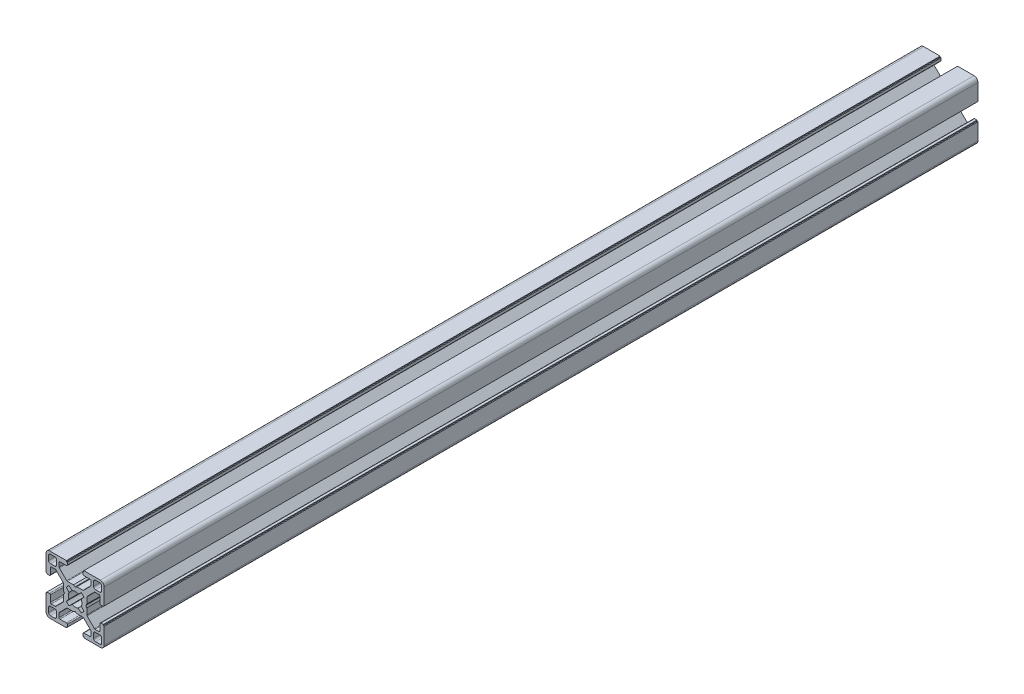
SolidWorks part; units mm, degrees
ref_plane "Front Plane" through (0, 0, 0) normal (0, 0, 1) x (1, 0, 0)
ref_plane "Top Plane" through (0, 0, 0) normal (0, 1, 0) x (1, 0, 0)
ref_plane "Right Plane" through (0, 0, 0) normal (1, 0, 0) x (0, 0, -1)
sketch "Sketch1" plane through (0, 0, 0) normal (0, 0, 1) x (1, 0, 0)
  line L0 (-15, 0) -> (15, 0) construction
  line L1 (0, -15) -> (0, 15) construction
  line L2 (-4.5, 15) -> (4.5, 15) construction
  line L3 (-4, -15) -> (4, -15) construction
  line L4 (-4.5, 15) -> (-4.5, 14.5)
  line L5 (-4.5, 14.5) -> (-4, 14.5)
  line L6 (-4, 14.5) -> (-4, 13.29)
  line L7 (-4.5, 12.79) -> (-7.7675, 12.79)
  line L8 (-8.2675, 12.29) -> (-8.2675, 10.2707)
  line L9 (-8.1211, 9.9171) -> (-4.3504, 6.1464)
  line L10 (-3.9968, 6) -> (0, 6)
  line L11 (0, 0) -> (-15, 15) construction
  line L12 (-4.5, 15) -> (-12.968, 15)
  line L14 (-12.705, 9.5135) -> (-10.5135, 9.5135)
  line L15 (-13.705, 10.5135) -> (-13.705, 12.705)
  line L16 (-12.705, 13.705) -> (-10.5135, 13.705)
  line L17 (-9.5135, 10.5135) -> (-9.5135, 12.705)
  line L18 (-13.705, 9.5135) -> (-9.5135, 13.705) construction
  line L19 (-13.705, 13.705) -> (-9.5135, 9.5135) construction
  line L20 (-3.1568, 4.5038) -> (-1.5303, 3.1477) construction
  line L21 (-4.5038, 3.1568) -> (-3.1477, 1.5303) construction
  line L22 (-6, 3.9968) -> (-6, 0)
  line L23 (-9.9171, 8.1211) -> (-6.1464, 4.3504)
  line L24 (-15, 4.5) -> (-15, 12.968)
  line L25 (-12.29, 8.2675) -> (-10.2707, 8.2675)
  line L26 (-12.79, 4.5) -> (-12.79, 7.7675)
  line L27 (-14.5, 4) -> (-13.29, 4)
  line L28 (-14.5, 4.5) -> (-14.5, 4)
  line L29 (-15, 4.5) -> (-14.5, 4.5)
  circle A0 centre (0, 0) radius 3.5
  arc A1 (-12.968, 15) -> (-15, 12.968) centre (-12.968, 12.968) ccw
  circle A2 centre (0, 0) radius 5.5 construction
  arc A3 (-10.5135, 9.5135) -> (-9.5135, 10.5135) centre (-10.5135, 10.5135) ccw
  arc A4 (-13.705, 12.705) -> (-12.705, 13.705) centre (-12.705, 12.705) cw
  arc A5 (-10.5135, 13.705) -> (-9.5135, 12.705) centre (-10.5135, 12.705) cw
  arc A6 (-12.705, 9.5135) -> (-13.705, 10.5135) centre (-12.705, 10.5135) cw
  arc A7 (-12.79, 4.5) -> (-13.29, 4) centre (-13.29, 4.5) cw
  arc A8 (-12.29, 8.2675) -> (-12.79, 7.7675) centre (-12.29, 7.7675) ccw
  arc A9 (-9.9171, 8.1211) -> (-10.2707, 8.2675) centre (-10.2707, 7.7675) ccw
  arc A10 (-6, 3.9968) -> (-6.1464, 4.3504) centre (-6.5, 3.9968) ccw
  arc A11 (-4.3504, 6.1464) -> (-3.9968, 6) centre (-3.9968, 6.5) ccw
  arc A12 (-4, 13.29) -> (-4.5, 12.79) centre (-4.5, 13.29) cw
  arc A13 (-7.7675, 12.79) -> (-8.2675, 12.29) centre (-7.7675, 12.29) ccw
  arc A14 (-8.2675, 10.2707) -> (-8.1211, 9.9171) centre (-7.7675, 10.2707) ccw
  point P4 (0, 0)
  point P8 (0, 0)
  point P13 (0, 15)
  point P15 (0, -15)
  point P16 (0, 6)
  point P23 (-11.6092, 11.6093)
  point P26 (0, 6)
  point P62 (-12.79, 4)
  point P65 (-12.79, 8.2675)
  point P68 (-10.0636, 8.2675)
  point P71 (-6, 4.2039)
  point P74 (-4.2039, 6)
  point P77 (-4, 12.79)
  point P80 (-8.2675, 12.79)
  point P83 (-8.2675, 10.0636)
  dimension "Center Hole Diameter" = 7
  dimension "D11" = 2.032
  dimension "D9" = 11
  dimension "D13" = 1
  dimension "D14" = 0.5
  dimension "Rail Height" = 30
  dimension "Rail Width" = 30
  dimension "T-Slot Width" = 8
  dimension "T-Slot Depth" = 9
  dimension "D1" = 9
  dimension "D2" = 45
  dimension "D3" = 8
  dimension "D4" = 2.21
  dimension "D5" = 16.535
  dimension "D7" = 2.54
  dimension "D6" = 1.295
  dimension "D8" = 1.246
  dimension "D10" = 10.36
  dimension "D12" = 1.905
sketch "Sketch2" plane through (0, 0, 0) normal (1, 0, 0) x (0, 0, -1)
  line L0 (-76.2, 0) -> (76.2, 0) construction
  line L2 (0, -15) -> (0, 15) construction
  line L3 (0, -15) -> (0, 15) construction
  line L4 (-76.2, -15) -> (-76.2, 15) construction
  line L5 (76.2, -15) -> (76.2, 15) construction
  point P0 (-38.7, 0)
  point P3 (0, 0)
  point P4 (38.7, 0)
  point P12 (-76.2, 0)
  point P14 (76.2, 0)
  dimension "Length" = 152.4
  dimension "D1" = 37.5
sketch "Sketch3" plane through (0, 0, 0) normal (0, 0, 1) x (1, 0, 0)
  line L0 (-4.5038, 3.1568) -> (-3.1477, 1.5303)
  line L1 (0, 3.5) -> (0, 5.5)
  line L2 (-5.5, 0) -> (-3.5, 0)
  line L7 (-6, 3.9968) -> (-6, 0) construction
  line L31 (-9.9171, 8.1211) -> (-6.1464, 4.3504) construction
  line L117 (-12.29, 8.2675) -> (-10.2707, 8.2675) construction
  line L118 (-12.79, 4.5) -> (-12.79, 7.7675) construction
  line L157 (-12.705, 9.5135) -> (-10.5135, 9.5135)
  line L158 (-9.5135, 10.5135) -> (-9.5135, 12.705)
  line L163 (-10.5135, 13.705) -> (-12.705, 13.705)
  line L164 (-13.705, 12.705) -> (-13.705, 10.5135)
  line L165 (-12.705, 9.5135) -> (-10.5135, 9.5135)
  line L166 (-9.5135, 10.5135) -> (-9.5135, 12.705)
  line L167 (-10.5135, 13.705) -> (-12.705, 13.705)
  line L168 (-13.705, 12.705) -> (-13.705, 10.5135)
  line L169 (-14.5, 4) -> (-13.29, 4) construction
  line L170 (-14.5, 4.5) -> (-14.5, 4) construction
  line L171 (-15, 4.5) -> (-14.5, 4.5) construction
  line L172 (-15, 4.5) -> (-15, 12.968) construction
  line L173 (-4.5, 15) -> (-12.968, 15) construction
  line L174 (-4.5, 15) -> (-4.5, 14.5) construction
  line L175 (-4.5, 14.5) -> (-4, 14.5) construction
  line L176 (-4, 14.5) -> (-4, 13.29) construction
  line L177 (-4.5, 12.79) -> (-7.7675, 12.79) construction
  line L178 (-8.2675, 12.29) -> (-8.2675, 10.2707) construction
  line L179 (-8.1211, 9.9171) -> (-4.3504, 6.1464) construction
  line L180 (-3.9968, 6) -> (0, 6) construction
  line L181 (-6, 3.9968) -> (-6, 0.866)
  line L182 (-9.9171, 8.1211) -> (-6.1464, 4.3504)
  line L183 (-12.29, 8.2675) -> (-10.2707, 8.2675)
  line L184 (-12.79, 4.5) -> (-12.79, 7.7675)
  line L185 (-14.5, 4) -> (-13.29, 4)
  line L186 (-14.5, 4.5) -> (-14.5, 4)
  line L187 (-15, 4.5) -> (-14.5, 4.5)
  line L188 (-15, 4.5) -> (-15, 12.968)
  line L189 (-4.5, 15) -> (-12.968, 15)
  line L190 (-4.5, 15) -> (-4.5, 14.5)
  line L191 (-4.5, 14.5) -> (-4, 14.5)
  line L192 (-4, 14.5) -> (-4, 13.29)
  line L193 (-4.5, 12.79) -> (-7.7675, 12.79)
  line L194 (-8.2675, 12.29) -> (-8.2675, 10.2707)
  line L195 (-8.1211, 9.9171) -> (-4.3504, 6.1464)
  line L196 (-3.9968, 6) -> (-0.866, 6)
  line L197 (-0.866, 6) -> (0, 5.5)
  line L198 (0, -15) -> (0, 15) construction
  line L199 (0, 0) -> (-15, 15) construction
  line L200 (0, 0) -> (-15, 15) construction
  line L201 (-3.1568, 4.5038) -> (-1.5303, 3.1477) construction
  line L202 (-3.1568, 4.5038) -> (-1.5303, 3.1477)
  line L203 (-6, 0.866) -> (-5.5, 0)
  line L204 (-15, 0) -> (15, 0) construction
  line L205 (-15, 0) -> (15, 0) construction
  line L206 (0, -15) -> (0, 15) construction
  arc A0 (-3.5, 0) -> (-3.1477, 1.5303) centre (0, 0) cw
  arc A10 (-6, 3.9968) -> (-6.1464, 4.3504) centre (-6.5, 3.9968) ccw construction
  circle A16 centre (0, 0) radius 3.5
  arc A18 (0, 3.5) -> (-1.5303, 3.1477) centre (0, 0) ccw
  arc A20 (-9.9171, 8.1211) -> (-10.2707, 8.2675) centre (-10.2707, 7.7675) ccw construction
  arc A22 (-12.29, 8.2675) -> (-12.79, 7.7675) centre (-12.29, 7.7675) ccw construction
  arc A28 (-13.29, 4) -> (-12.79, 4.5) centre (-13.29, 4.5) ccw construction
  arc A29 (-10.5135, 9.5135) -> (-9.5135, 10.5135) centre (-10.5135, 10.5135) ccw
  arc A30 (-9.5135, 12.705) -> (-10.5135, 13.705) centre (-10.5135, 12.705) ccw
  arc A31 (-12.705, 13.705) -> (-13.705, 12.705) centre (-12.705, 12.705) ccw
  arc A32 (-13.705, 10.5135) -> (-12.705, 9.5135) centre (-12.705, 10.5135) ccw
  arc A33 (-10.5135, 9.5135) -> (-9.5135, 10.5135) centre (-10.5135, 10.5135) ccw
  arc A34 (-9.5135, 12.705) -> (-10.5135, 13.705) centre (-10.5135, 12.705) ccw
  arc A35 (-12.705, 13.705) -> (-13.705, 12.705) centre (-12.705, 12.705) ccw
  arc A36 (-13.705, 10.5135) -> (-12.705, 9.5135) centre (-12.705, 10.5135) ccw
  arc A37 (-12.968, 15) -> (-15, 12.968) centre (-12.968, 12.968) ccw construction
  arc A38 (-4.5, 12.79) -> (-4, 13.29) centre (-4.5, 13.29) ccw construction
  arc A39 (-7.7675, 12.79) -> (-8.2675, 12.29) centre (-7.7675, 12.29) ccw construction
  arc A40 (-8.2675, 10.2707) -> (-8.1211, 9.9171) centre (-7.7675, 10.2707) ccw construction
  arc A41 (-4.3504, 6.1464) -> (-3.9968, 6) centre (-3.9968, 6.5) ccw construction
  arc A42 (-6, 3.9968) -> (-6.1464, 4.3504) centre (-6.5, 3.9968) ccw
  arc A43 (-9.9171, 8.1211) -> (-10.2707, 8.2675) centre (-10.2707, 7.7675) ccw
  arc A44 (-12.29, 8.2675) -> (-12.79, 7.7675) centre (-12.29, 7.7675) ccw
  arc A45 (-13.29, 4) -> (-12.79, 4.5) centre (-13.29, 4.5) ccw
  arc A46 (-12.968, 15) -> (-15, 12.968) centre (-12.968, 12.968) ccw
  arc A47 (-4.5, 12.79) -> (-4, 13.29) centre (-4.5, 13.29) ccw
  arc A48 (-7.7675, 12.79) -> (-8.2675, 12.29) centre (-7.7675, 12.29) ccw
  arc A49 (-8.2675, 10.2707) -> (-8.1211, 9.9171) centre (-7.7675, 10.2707) ccw
  arc A50 (-4.3504, 6.1464) -> (-3.9968, 6) centre (-3.9968, 6.5) ccw
  circle A51 centre (0, 0) radius 5.5 construction
  arc A52 (-3.1568, 4.5038) -> (-4.5038, 3.1568) centre (0, 0) ccw
  dimension "D3" = 60
  dimension "D4" = 60
  dimension "D1" = 0
  dimension "D2" = 0
extrude "Boss-Extrude1" add sketch "Sketch3" along normal mid plane 450
pattern_circular "CirPattern1" count 4 over 360 about axis through (0, 0, 76.2) along (0, 0, -1) of "Boss-Extrude1"
ref_plane "Contact Plane1" through (15, 0, 0) normal (1, 0, 0) x (0, 0, -1)
ref_plane "Contact Plane2" through (0, -15, 0) normal (0, 1, 0) x (1, 0, 0)
ref_plane "Contact Plane3" through (-15, 0, 0) normal (1, 0, 0) x (0, 0, -1)
ref_plane "Contact Plane4" through (0, 15, 0) normal (0, 1, 0) x (1, 0, 0)
equation "\"D1@Sketch2\" = \"Rail Height@Sketch1\" * 1.25"
equation "\"D1@Sketch1\"=\"T-Slot Width@Sketch1\"+1mm"
equation "\"D3@Sketch1\"=\"T-Slot Width@Sketch1\""
equation "\"D1@Boss-Extrude1\"=\"length\""
equation "\"length\" = 450"
